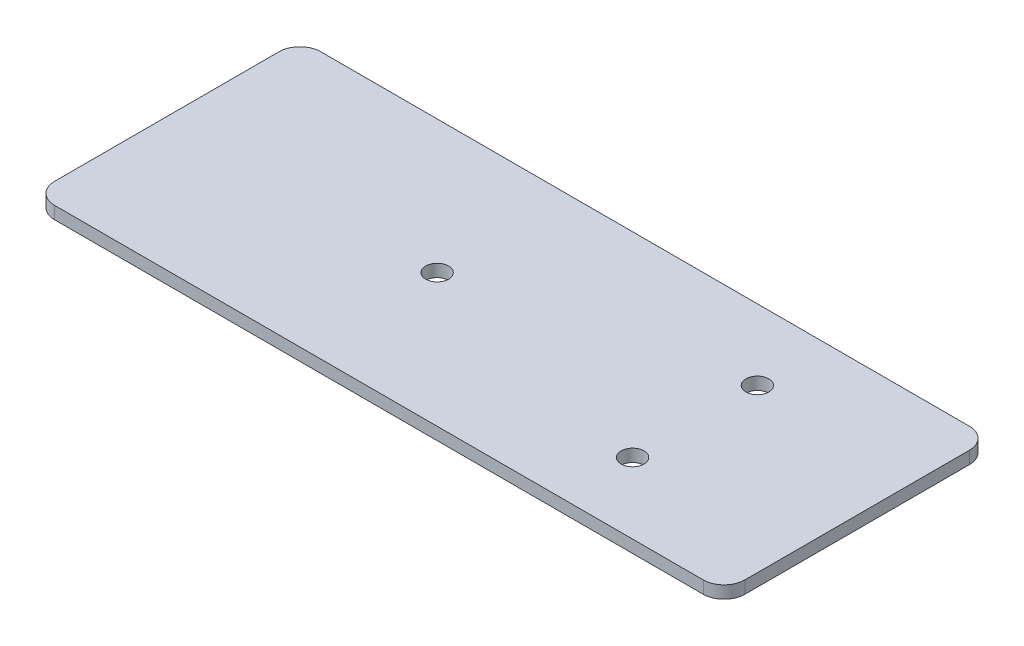
SolidWorks part; units mm, degrees
material "ABS PC"
ref_plane "Front Plane" through (0, 0, 0) normal (0, 0, 1) x (1, 0, 0)
ref_plane "Top Plane" through (0, 0, 0) normal (0, 1, 0) x (1, 0, 0)
ref_plane "Right Plane" through (0, 0, 0) normal (1, 0, 0) x (0, 0, -1)
sketch "Sketch1" plane through (0, 0, 0) normal (0, 1, 0) x (1, 0, 0)
  line L1 (78, 32) -> (-78, 32)
  line L2 (83, 27) -> (83, -27)
  line L3 (78, -32) -> (-78, -32)
  line L4 (-83, 27) -> (-83, -27)
  line L5 (83, 32) -> (-83, -32) construction
  line L6 (83, -32) -> (-83, 32) construction
  arc A0 (78, 32) -> (83, 27) centre (78, 27) cw
  arc A1 (83, -27) -> (78, -32) centre (78, -27) cw
  arc A2 (-78, -32) -> (-83, -27) centre (-78, -27) cw
  arc A3 (-78, 32) -> (-83, 27) centre (-78, 27) ccw
  point P0 (0, 0)
  dimension "D1" = 5
  dimension "D2" = 166
  dimension "D3" = 64
extrude "Boss-Extrude1" add sketch "Sketch1" along normal blind 3
sketch "Sketch2" plane through (0, 3, 0) normal (0, 1, 0) x (1, 0, 0)
  line L0 (-83, 0) -> (83, 0) construction
  line L1 (-83, 27) -> (-83, -27) construction
  line L2 (83, -27) -> (83, 27) construction
  circle A0 centre (44, -15) radius 2.75
  circle A1 centre (44, 15) radius 2.75
  circle A2 centre (-18, 0) radius 2.75
  dimension "D1" = 30
  dimension "D3" = 5.5
  dimension "D4" = 62
  dimension "D2" = 127
extrude "Cut-Extrude1" cut sketch "Sketch2" against normal through all
